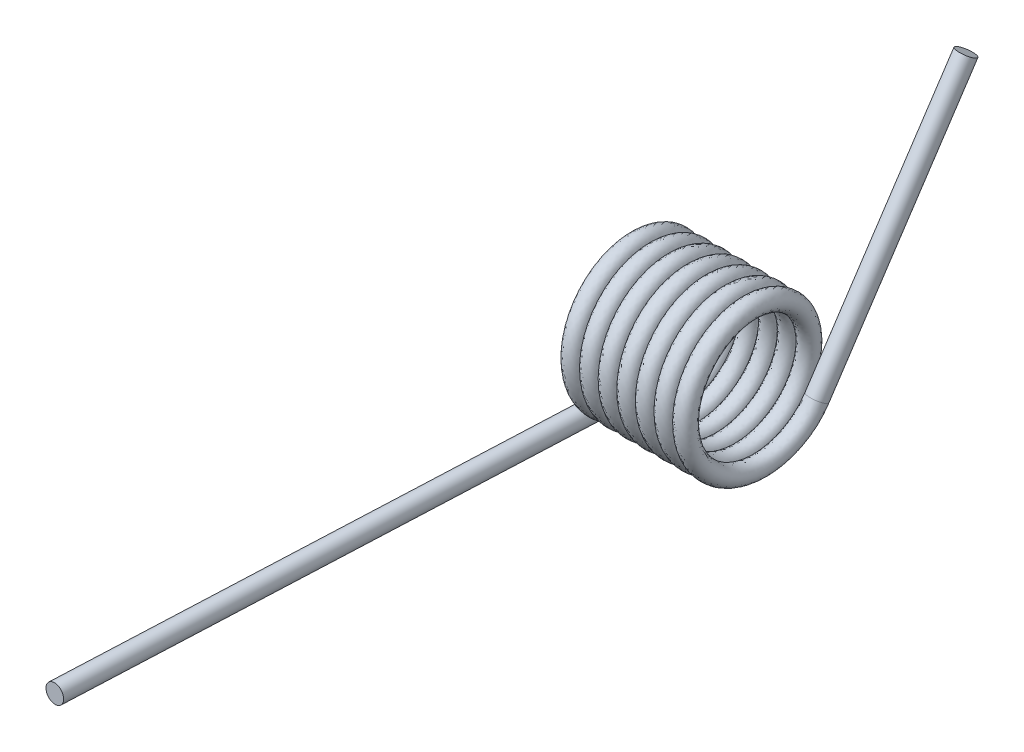
SolidWorks part; units mm, degrees
ref_plane "Front" through (0, 0, 0) normal (0, 0, 1) x (1, 0, 0)
ref_plane "Top" through (0, 0, 0) normal (0, 1, 0) x (1, 0, 0)
ref_plane "Right" through (0, 0, 0) normal (1, 0, 0) x (0, 0, -1)
sketch "Sketch1" plane through (0, 0, 0) normal (1, 0, 0) x (0, 0, -1)
  line L0 (0, -10.5664) -> (0, -13.9954) construction
  line L1 (12.1204, -6.9977) -> (62.9204, 80.9905) construction
  line L2 (0, -13.9954) -> (-101.6, -13.9954) construction
  line L3 (0, 0) -> (13.9954, 0) construction
  line L4 (0, 0) -> (12.1204, -6.9977) construction
  line L5 (-101.6, -13.9954) -> (-101.6, -10.5664) construction
  line L6 (-101.6, -10.5664) -> (0, -10.5664) construction
  line L7 (62.9204, 80.9905) -> (59.9508, 82.705) construction
  line L8 (59.9508, 82.705) -> (9.1508, -5.2832) construction
  circle A0 centre (0, 0) radius 13.9954 construction
  circle A1 centre (0, 0) radius 8.4582 construction
  circle A2 centre (0, 0) radius 12.2809 construction
  point P7 (0, -12.2809)
  point P10 (0, 13.9954)
  dimension "OD" = 27.9908
  dimension "For Shaft Diameter" = 16.9164
  dimension "Wire Diameter" = 3.429
  dimension "Leg Length" = 101.6
  dimension "Deflection Angle" = 120
sketch "Sketch2" plane through (0, 0, 0) normal (1, 0, 0) x (0, 0, -1)
  circle A0 centre (0, 0) radius 12.2809 construction
  circle A2 centre (0, 0) radius 12.2809
curve "Helix/Spiral1" pitch 3.4544 height 24.7565 radius 12.2809 centre (0, 0, 0) axis (1, 0, 0) start towards (0, 0, -1)
ref_plane "Plane1" through (0, -12.2809, 0) normal (0.0447, 0, -0.999) x (0.9987, -0.0232, 0.0447)
sketch "Sketch3" plane through (0, -12.2809, 0) normal (0.0447, 0, -0.999) x (0.9987, -0.0232, 0.0447)
  circle A0 centre (0, 0) radius 1.7145
  dimension "D1" = 3.429
sweep "Sweep1" add profiles "Sketch3" path "Helix/Spiral1"
sketch "Sketch4" plane through (0, 0, 0) normal (-0.0447, 0, 0.999) x (-0.9987, 0.0232, -0.0447)
  circle A1 centre (-0.2854, 12.2776) radius 1.7145
  circle A2 centre (-0.2854, 12.2776) radius 1.7145
  dimension "D1" = 0
extrude "Extrude1" add sketch "Sketch4" along normal blind 101.6
sketch "Sketch5" plane through (0.0495, 0.9579, -0.553) normal (0.0447, 0.8652, -0.4995) x (0.9979, -0.0623, -0.0185)
  circle A1 centre (25.284, 11.0996) radius 1.7145
  circle A2 centre (25.284, 11.0996) radius 1.7145
  dimension "D1" = 0
extrude "Extrude2" add sketch "Sketch5" along normal blind 50.8
sketch "Sketch6" plane through (0, 0, 0) normal (1, 0, 0) x (0, 0, -1)
  circle A2 centre (0, 0) radius 10.5664 construction
equation "\"D4@Helix/Spiral1\" = \"Wire Diameter@Sketch1\" + .001"
equation "\"D1@Sketch3\"=\"Wire Diameter@Sketch1\""
